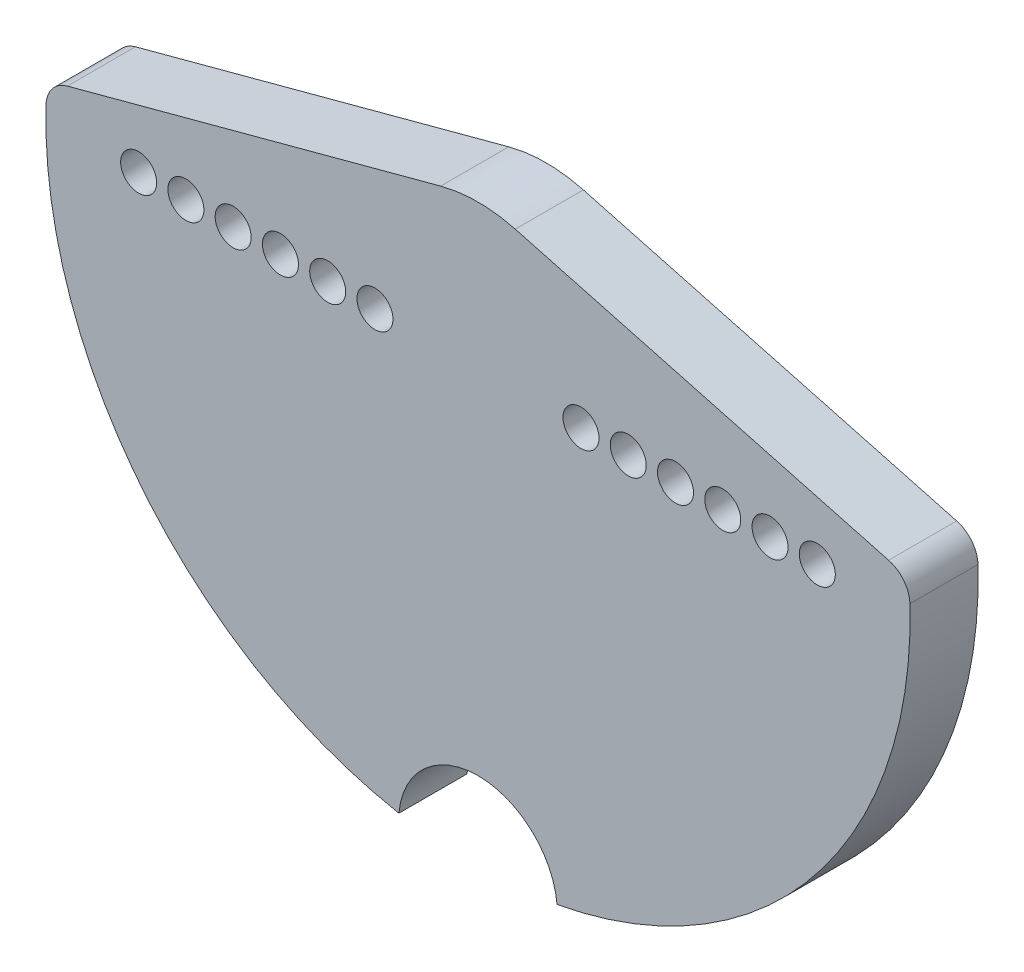
SolidWorks part; units mm, degrees
ref_plane "Front Plane" through (0, 0, 0) normal (0, 0, 1) x (1, 0, 0)
ref_plane "Top Plane" through (0, 0, 0) normal (0, 1, 0) x (1, 0, 0)
ref_plane "Right Plane" through (0, 0, 0) normal (1, 0, 0) x (0, 0, -1)
sketch "Sketch1" plane through (0, 0, 0) normal (0, 0, 1) x (1, 0, 0)
  line L0 (1.6435, 6.1336) -> (18.1018, 1.7237)
  line L1 (0, 0) -> (0, -19.05) construction
  line L2 (-3.4852, -18.7285) -> (0, -19.05) construction
  line L3 (-1.6435, 6.1336) -> (-18.1018, 1.7237)
  arc A1 (-19.0426, 0.5324) -> (-3.4852, -18.7285) centre (0, 0) ccw
  arc A2 (-3.4852, -18.7285) -> (3.4852, -18.7285) centre (0, -19.05) cw
  arc A3 (-18.1018, 1.7237) -> (-19.0426, 0.5324) centre (-17.7731, 0.4969) ccw
  arc A4 (-1.6435, 6.1336) -> (1.6435, 6.1336) centre (0, 0) cw
  arc A5 (19.0426, 0.5324) -> (3.4852, -18.7285) centre (0, 0) cw
  arc A6 (18.1018, 1.7237) -> (19.0426, 0.5324) centre (17.7731, 0.4969) cw
  dimension "D1" = 3.5
  dimension "D3" = 19.05
  dimension "D4" = 1.27
  dimension "D2" = 6.35
  dimension "D7" = 75
extrude "Boss-Extrude1" add sketch "Sketch1" along normal blind 3
sketch "Sketch2" plane through (0, 0, 3) normal (0, 0, 1) x (1, 0, 0)
  circle A1 centre (-12.875, 0) radius 0.375
  circle A6 centre (-12.875, 0) radius 0.375 construction
  circle A7 centre (-14.9583, 0) radius 0.375
  circle A8 centre (-14.9583, 0) radius 0.375 construction
  circle A9 centre (-4.5417, 0) radius 0.375
  circle A10 centre (-4.5417, 0) radius 0.375 construction
  circle A11 centre (-6.625, 0) radius 0.375
  circle A12 centre (-6.625, 0) radius 0.375 construction
  circle A13 centre (-8.7083, 0) radius 0.375
  circle A14 centre (-8.7083, 0) radius 0.375 construction
  circle A15 centre (-10.7917, 0) radius 0.375
  circle A16 centre (-10.7917, 0) radius 0.375 construction
  circle A24 centre (-12.875, 0) radius 0.7938
  circle A25 centre (-14.9583, 0) radius 0.7937
  circle A26 centre (-4.5417, 0) radius 0.7938
  circle A27 centre (-6.625, 0) radius 0.7938
  circle A28 centre (-8.7083, 0) radius 0.7938
  circle A29 centre (-10.7917, 0) radius 0.7938
  point P0 (0, 0)
  dimension "D1" = 1.5875
  dimension "D2" = 0
  dimension "D3" = 0
  dimension "D4" = 0
  dimension "D5" = 0
  dimension "D6" = 0
  dimension "D7" = 0
extrude "Cut-Extrude1" cut sketch "Sketch2" against normal through all both and the other way through all
mirror "Mirror1" about plane through (0, 0, 0) normal (1, 0, 0) of "Cut-Extrude1"
